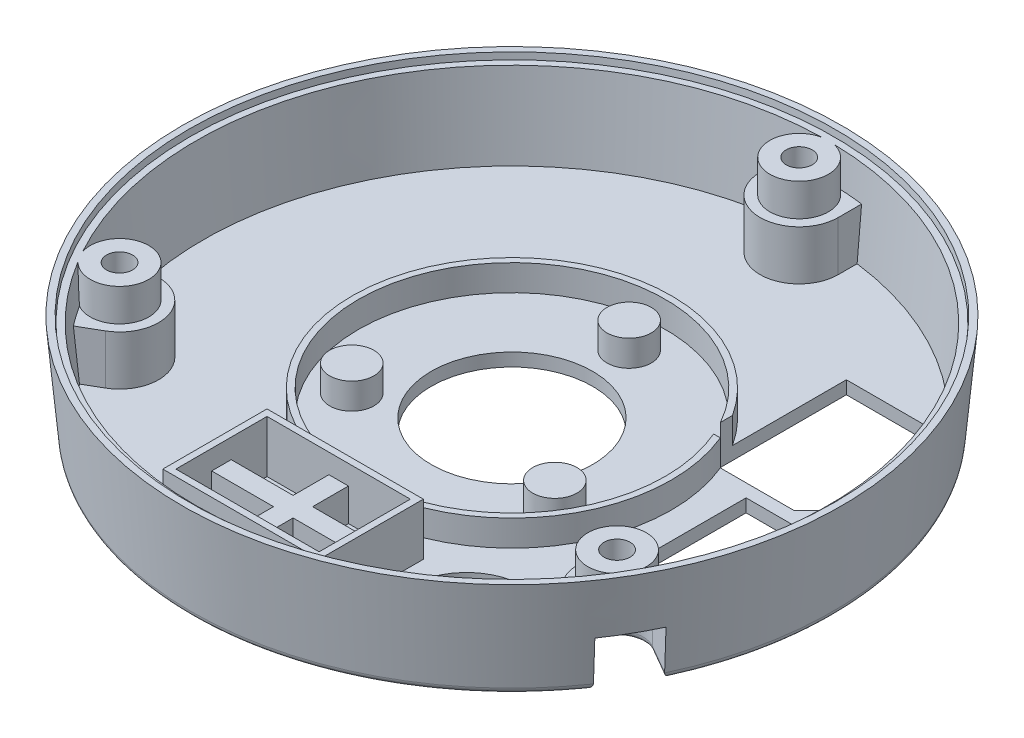
SolidWorks part; units mm, degrees
ref_plane "前视基准面" through (0, 0, 0) normal (0, 0, 1) x (1, 0, 0)
ref_plane "上视基准面" through (0, 0, 0) normal (0, 1, 0) x (1, 0, 0)
ref_plane "右视基准面" through (0, 0, 0) normal (1, 0, 0) x (0, 0, -1)
sketch "草图7" plane through (0, 0, 0) normal (0, 0, 1) x (1, 0, 0)
  line L0 (0, 0) -> (24.6, 0)
  line L1 (24.6, 0) -> (25.3, 7.8)
  line L2 (25.3, 7.8) -> (24.8, 7.8)
  line L3 (24.2551, 7.3) -> (23.6897, 1)
  line L4 (23.6897, 1) -> (0, 1)
  line L5 (0, 1) -> (0, 0)
  line L6 (24.8, 7.8) -> (24.7551, 7.3)
  line L7 (24.7551, 7.3) -> (24.2551, 7.3)
  dimension "D1" = 24.6
  dimension "D2" = 25.3
  dimension "D4" = 1
  dimension "D5" = 7.8
  dimension "D6" = 0.5
revolve "旋转1" add sketch "草图7" angle 360 about L5
sketch "草图8" plane through (0, 1, 0) normal (0, 1, 0) x (1, 0, 0)
  line L0 (-3, 22.05) -> (-3, 24.1141)
  line L1 (0, 22.05) -> (-19.0959, -11.025) construction
  line L2 (-19.0959, -11.025) -> (19.0959, -11.025) construction
  line L3 (19.0959, -11.025) -> (0, 22.05) construction
  line L4 (3, 22.05) -> (3, 24.1141)
  circle A0 centre (0, 0) radius 11.025 construction
  circle A1 centre (0, 22.05) radius 1
  circle A2 centre (0, 22.05) radius 2.25
  arc A3 (-3, 22.05) -> (3, 22.05) centre (0, 22.05) ccw
  circle A4 centre (0, 0) radius 24.3 construction
  arc A6 (-3, 24.1141) -> (3, 24.1141) centre (0, 0) cw
  dimension "D1" = 2
  dimension "D2" = 4.5
  dimension "D3" = 6
extrude "凸台-拉伸23" add sketch "草图8" along normal up to surface (6.3 mm away) contours A2 up to face at (-24.2551, 7.3, 0)
extrude "凸台-拉伸24" add sketch "草图8<4>" along normal blind 3.8 contours A6 L4 A3 L0
sketch "草图8<4>" plane through (0, 1, 0) normal (0, 1, 0) x (1, 0, 0) same geometry as "草图8"
extrude "切除-拉伸2" cut sketch "草图8<5>" against normal through all both and the other way through all contours A1
sketch "草图8<5>" plane through (0, 1, 0) normal (0, 1, 0) x (1, 0, 0) same geometry as "草图8"
pattern_circular "阵列(圆周)1" count 3 over 360 about axis through (0, 1, 0) along (0, 1, 0) of "凸台-拉伸23", "凸台-拉伸24", "切除-拉伸2"
sketch "草图9" plane through (0, 0, 0) normal (0, -1, 0) x (1, 0, 0)
  line L0 (2, -22.05) -> (2, -26.0952)
  line L1 (2, -26.0952) -> (-2, -26.0952)
  line L2 (-2, -26.0952) -> (-2, -22.05)
  arc A0 (2, -22.05) -> (-2, -22.05) centre (0, -22.05) ccw
  dimension "D1" = 4
extrude "切除-拉伸3" cut sketch "草图9" against normal blind 3.7 contours L2 A0 L0 L1
pattern_circular "阵列(圆周)2" count 3 over 360 about axis through (0, 0, 0) along (0, 1, 0) of "切除-拉伸3"
sketch "草图11" plane through (0, 1, 0) normal (0, 1, 0) x (1, 0, 0)
  line L0 (0, 0) -> (0, 22.05) construction
  line L1 (10.3, 15.375) -> (10.3, 4.675)
  line L2 (10.3, 4.675) -> (17, 4.675)
  line L4 (19, 6.675) -> (19, 13.375)
  line L6 (17, 15.375) -> (10.3, 15.375)
  line L7 (10.3, 15.375) -> (10.3, 21.3334) construction
  line L8 (14.3, 3.675) -> (14.3, -7.025)
  line L9 (14.3, -7.025) -> (21, -7.025)
  line L10 (23, -5.025) -> (23, 1.675)
  line L11 (21, 3.675) -> (14.3, 3.675)
  line L12 (19.0959, -8.025) -> (9.5, -8.025) construction
  line L15 (21, -7.025) -> (23, -5.025)
  line L16 (23, 1.675) -> (21, 3.675)
  line L17 (17, 4.675) -> (19, 6.675)
  line L18 (19, 13.375) -> (17, 15.375)
  arc A1 (21.8507, -9.1514) -> (3, 23.499) centre (0, 0) ccw construction
  arc A2 (20.5959, -8.4269) -> (17.5959, -13.6231) centre (19.0959, -11.025) ccw construction
  point P6 (23, -7.025)
  point P7 (23, 3.675)
  point P10 (19, 15.375)
  point P21 (19, 4.675)
  dimension "D1" = 10.3
  dimension "D2" = 8.7
  dimension "D3" = 10.7
  dimension "D4" = 1
  dimension "D5" = 1
  dimension "D6" = 4
  dimension "D7" = 8.7
  dimension "D8" = 10.7
extrude "切除-拉伸6" cut sketch "草图11" against normal up to surface (1 mm away) up to face at (0, 0, 0)
sketch "草图12" plane through (0, 1, 0) normal (0, 1, 0) x (1, 0, 0)
  line L0 (-5.5, -13.3) -> (-5.5, -20.3)
  line L1 (-5.5, -20.3) -> (5.5, -20.3)
  line L2 (5.5, -20.3) -> (5.5, -13.3)
  line L3 (5.5, -13.3) -> (-5.5, -13.3)
  line L4 (-18.1727, -25.3) -> (19.526, -25.3) construction
  circle A1 centre (0, 0) radius 25.3 construction
  point P3 (0, -13.3)
  dimension "D1" = 12
  dimension "D2" = 5
  dimension "D3" = 11
extrude "拉伸-薄壁1" add sketch "草图12" along normal blind 4 thin thin type one direction wall 0.5
sketch "草图13" plane through (0, 0, 0) normal (0, -1, 0) x (-1, 0, 0)
  line L0 (24.6, 19.236) -> (24.6, -17.3672) construction
  line L1 (6.6, 23.6981) -> (6.6, -23.6981) construction
  arc A0 (22.2337, -10.5272) -> (2, 24.5186) centre (0, 0) ccw construction
  arc A1 (-20.2337, -13.9913) -> (20.2337, -13.9913) centre (0, 0) ccw construction
  dimension "D1" = 18
sketch "草图14" plane through (0, 1, 0) normal (0, 1, 0) x (1, 0, 0)
  circle A0 centre (0, 0) radius 11.7 construction
  circle A2 centre (0, 0) radius 6.2
  circle A3 centre (11.7077, -15.2045) radius 4.5
  arc A4 (-18.8507, -14.3476) -> (18.8507, -14.3476) centre (0, 0) ccw construction
  dimension "D1" = 23.4
  dimension "D2" = 12.4
  dimension "D3" = 9
extrude "切除-拉伸7" cut sketch "草图14" against normal up to surface (1 mm away) up to face at (19.4333, 0, 1.675)
fillet "圆角1" radius 0.5 12 edges at (17.3638, 0, 10.025) (21.1648, 0, 9.9101) (-21.1648, 0, 9.9101) (-17.3638, 0, 10.025) (-19.1648, 0, 13.3742) (-21.3042, 0, -12.3) (-2, 0, -23.2843) (0, 0, -20.05) (2, 0, -23.2843) (21.3042, 0, -12.3) (19.1648, 0, 13.3742) (0, 0, 24.6)
sketch "草图15" plane through (0, 1, 0) normal (0, 1, 0) x (1, 0, 0)
  line L0 (5.5, -20.3) -> (5.5, -13.3) construction
  line L1 (5.5, -17.55) -> (-5.5, -17.55)
  line L2 (5.5, -17.55) -> (5.5, -16.05)
  line L3 (5.5, -16.05) -> (-5.5, -16.05)
  line L4 (-5.5, -17.55) -> (-5.5, -16.05)
  line L5 (-5.5, -13.3) -> (-5.5, -20.3) construction
  line L6 (5.5, -13.3) -> (-5.5, -13.3) construction
  line L7 (-0.75, -13.3) -> (0.75, -13.3)
  line L8 (-0.75, -13.3) -> (-0.75, -20.3)
  line L9 (-0.75, -20.3) -> (0.75, -20.3)
  line L10 (0.75, -13.3) -> (0.75, -20.3)
  line L11 (-5.5, -20.3) -> (5.5, -20.3) construction
  line L12 (5.5, -20.3) -> (5.5, -13.3) construction
  line L13 (-5.5, -20.3) -> (5.5, -20.3) construction
  point P18 (5.5, -16.8)
  point P19 (5.5, -16.8)
  point P22 (0, -20.3)
  point P23 (0, -20.3)
  line M2 (5.5, -13.3) -> (-5.5, -13.3)
  line M4 (-5.5, -20.3) -> (5.5, -20.3)
  dimension "D1" = 1.5
  dimension "D2" = 1.5
extrude "凸台-拉伸25" add sketch "草图15" along normal blind 2.5 contours L10 L1 L8 M4 | L10 L8 L3 M2 | L3 L4 L1 L2 region at (0, 1, 18.925) region at (0, 1, 14.675)
sketch "草图16" plane through (0, 1, 0) normal (0, 1, 0) x (1, 0, 0)
  line L0 (0, 0) -> (0, 22.05) construction
  circle A0 centre (0, 0) radius 11.775
  circle A1 centre (0, 0) radius 12.25
  circle A2 centre (0, 0) radius 9 construction
  circle A3 centre (0, 9) radius 1.7
  circle A4 centre (7.7942, -4.5) radius 1.7
  circle A5 centre (-7.7942, -4.5) radius 1.7
  line M18 (17, 4.675) -> (10.3, 4.675)
  line M19 (10.3, 4.675) -> (10.3, 15.375)
  dimension "D1" = 23.55
  dimension "D2" = 24.5
  dimension "D3" = 18
  dimension "D4" = 3.4
  dimension "D5" = 3
extrude "凸台-拉伸26" add sketch "草图16" along normal blind 2 contours A1 A0 M19 M18 | A3 | A4 | A5 region at (11.8698, 1, -2.4573) region at (0, 1, -9) region at (7.7942, 1, 4.5) region at (-7.7942, 1, 4.5)
